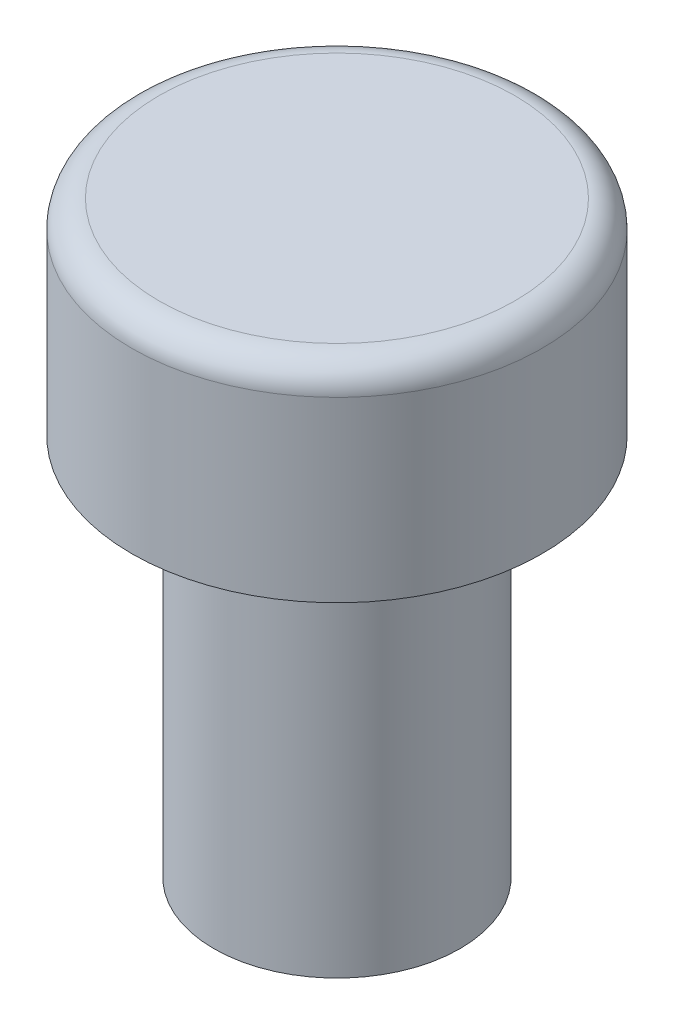
SolidWorks part; units mm, degrees
ref_plane "Front Plane" through (0, 0, 0) normal (0, 0, 1) x (1, 0, 0)
ref_plane "Top Plane" through (0, 0, 0) normal (0, 1, 0) x (1, 0, 0)
ref_plane "Right Plane" through (0, 0, 0) normal (1, 0, 0) x (0, 0, -1)
sketch "Sketch1" plane through (0, 0, 0) normal (0, 1, 0) x (1, 0, 0)
  circle A0 centre (0, 0) radius 7.5
  dimension "D1" = 15
extrude "Boss-Extrude1" add sketch "Sketch1" along normal blind 7.5
fillet "Fillet1" radius 1 1 edges at (0, 7.5, 7.5)
sketch "Sketch2" plane through (0, 0, 0) normal (0, -1, 0) x (1, 0, 0)
  circle A0 centre (0, 0) radius 4.5
  dimension "D1" = 9
extrude "Boss-Extrude2" add sketch "Sketch2" along normal blind 14
sketch "Sketch3" plane through (0, -14, 0) normal (0, -1, 0) x (-1, 0, 0)
  circle A0 centre (0, 0) radius 3
  dimension "D1" = 6
extrude "Cut-Extrude1" cut sketch "Sketch3" against normal blind 11
sketch "Sketch4" plane through (0, -3, 0) normal (0, -1, 0) x (-1, 0, 0)
  line L0 (1.75, -2.4367) -> (1.75, 2.4367)
  circle A0 centre (0, 0) radius 3 construction
  circle A1 centre (0, 0) radius 3
  circle M2 centre (0, 0) radius 3
  dimension "D1" = 1.75
  dimension "D2" = 6
extrude "Boss-Extrude3" add sketch "Sketch4" along normal up to surface (11 mm away) contours L0 M2 region at (-2.2602, -3, 0) up to face at (0, -14, -3)
